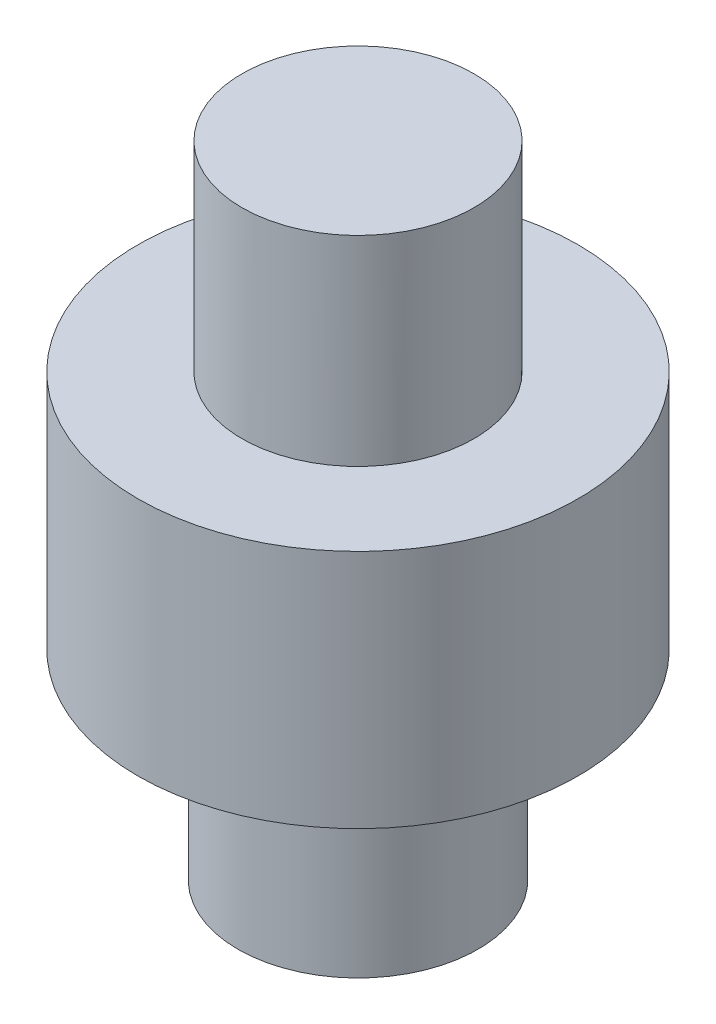
SolidWorks part; units mm, degrees
ref_plane "Front" through (0, 0, 0) normal (0, 0, 1) x (1, 0, 0)
ref_plane "Top" through (0, 0, 0) normal (0, 1, 0) x (1, 0, 0)
ref_plane "Right" through (0, 0, 0) normal (1, 0, 0) x (0, 0, -1)
sketch "Sketch1" plane through (0, 0, 0) normal (0, 1, 0) x (1, 0, 0)
  circle A0 centre (0, 0) radius 1.45
  circle A1 centre (0, 0) radius 3.25 construction
  dimension "D1" = 2.9
extrude "Boss-Extrude1" add sketch "Sketch1" along normal blind 2.5
sketch "Sketch2" plane through (0, 0, 0) normal (0, -1, 0) x (1, 0, 0)
  circle A0 centre (0, 0) radius 2.75
  dimension "D1" = 5.5
extrude "Boss-Extrude2" add sketch "Sketch2" along normal blind 3
sketch "Sketch3" plane through (0, -3, 0) normal (0, -1, 0) x (1, 0, 0)
  circle A0 centre (0, 0) radius 1.5
  dimension "D1" = 3
extrude "Boss-Extrude3" add sketch "Sketch3" along normal blind 2.5
